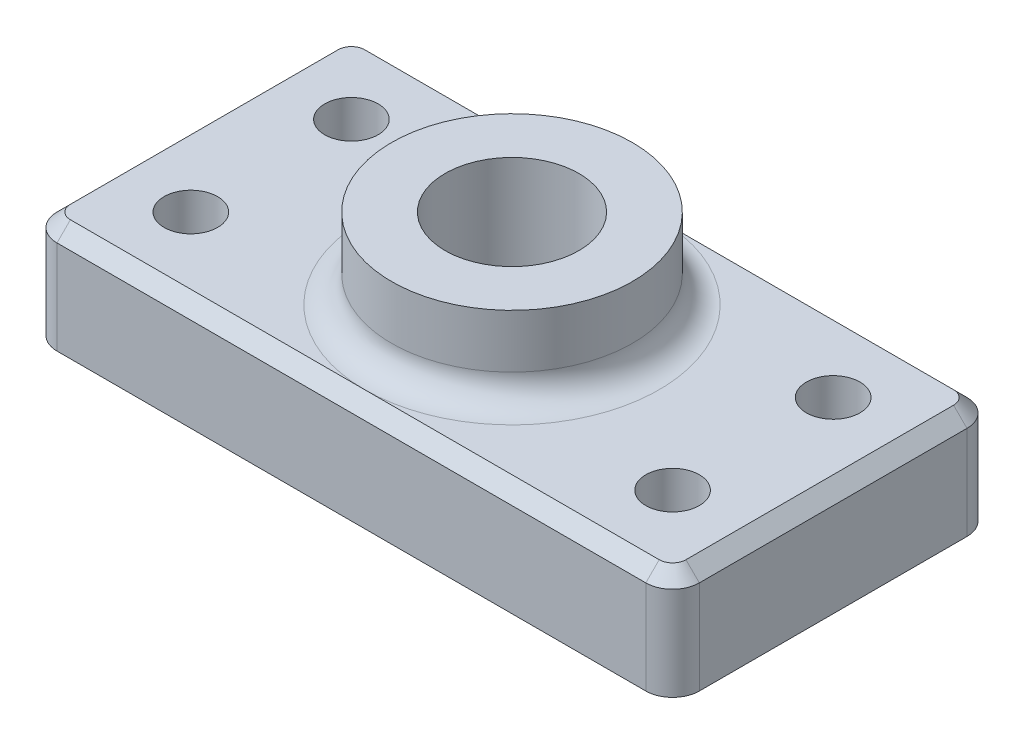
SolidWorks part; units mm, degrees
ref_plane "Front Plane" through (0, 0, 0) normal (0, 0, 1) x (1, 0, 0)
ref_plane "Top Plane" through (0, 0, 0) normal (0, 1, 0) x (1, 0, 0)
ref_plane "Right Plane" through (0, 0, 0) normal (1, 0, 0) x (0, 0, -1)
sketch "Sketch1" plane through (0, 0, 0) normal (0, 1, 0) x (1, 0, 0)
  line L1 (-76.2, 38.1) -> (76.2, 38.1)
  line L2 (-76.2, 38.1) -> (-76.2, -38.1)
  line L3 (-76.2, -38.1) -> (76.2, -38.1)
  line L4 (76.2, 38.1) -> (76.2, -38.1)
  line L5 (-76.2, 38.1) -> (76.2, -38.1) construction
  line L6 (-76.2, -38.1) -> (76.2, 38.1) construction
  point P0 (0, 0)
  dimension "D1" = 152.4
  dimension "D2" = 76.2
extrude "Boss-Extrude1" add sketch "Sketch1" along normal blind 25.4
sketch "Sketch2" plane through (0, 25.4, 0) normal (0, 1, 0) x (1, 0, 0)
  line L0 (-76.2, 38.1) -> (-76.2, -38.1) construction
  line L1 (76.2, 38.1) -> (-76.2, 38.1) construction
  line L2 (0, 0) -> (-97.6466, 0) construction
  line L3 (0, 0) -> (0, 48.5354) construction
  circle A0 centre (-57.15, 19.05) radius 6.35
  circle A1 centre (-57.15, -19.05) radius 6.35
  circle A2 centre (57.15, -19.05) radius 6.35
  circle A3 centre (57.15, 19.05) radius 6.35
  dimension "D1" = 12.7
  dimension "D2" = 19.05
  dimension "D3" = 19.05
extrude "Cut-Extrude1" cut sketch "Sketch2" against normal through all
sketch "Sketch3" plane through (0, 25.4, 0) normal (0, 1, 0) x (1, 0, 0)
  circle A0 centre (0, 0) radius 28.575
  dimension "D1" = 57.15
extrude "Boss-Extrude2" add sketch "Sketch3" along normal blind 19.05 contours A0
sketch "Sketch4" plane through (0, 44.45, 0) normal (0, 1, 0) x (1, 0, 0)
  circle A0 centre (0, 0) radius 15.875
  dimension "D1" = 31.75
extrude "Cut-Extrude3" cut sketch "Sketch4" against normal through all
fillet "Fillet1" radius 6.35 5 edges at (-76.2, 12.7, -38.1) (76.2, 12.7, -38.1) (76.2, 12.7, 38.1) (-76.2, 12.7, 38.1) (0, 25.4, 28.575)
chamfer "Chamfer1" distance 3.175 angle 45 8 edges at (76.2, 25.4, 0) (74.3401, 25.4, -36.2401) (74.3401, 25.4, 36.2401) (0, 25.4, -38.1) (0, 25.4, 38.1) (-74.3401, 25.4, -36.2401) (-74.3401, 25.4, 36.2401) (-76.2, 25.4, 0)
